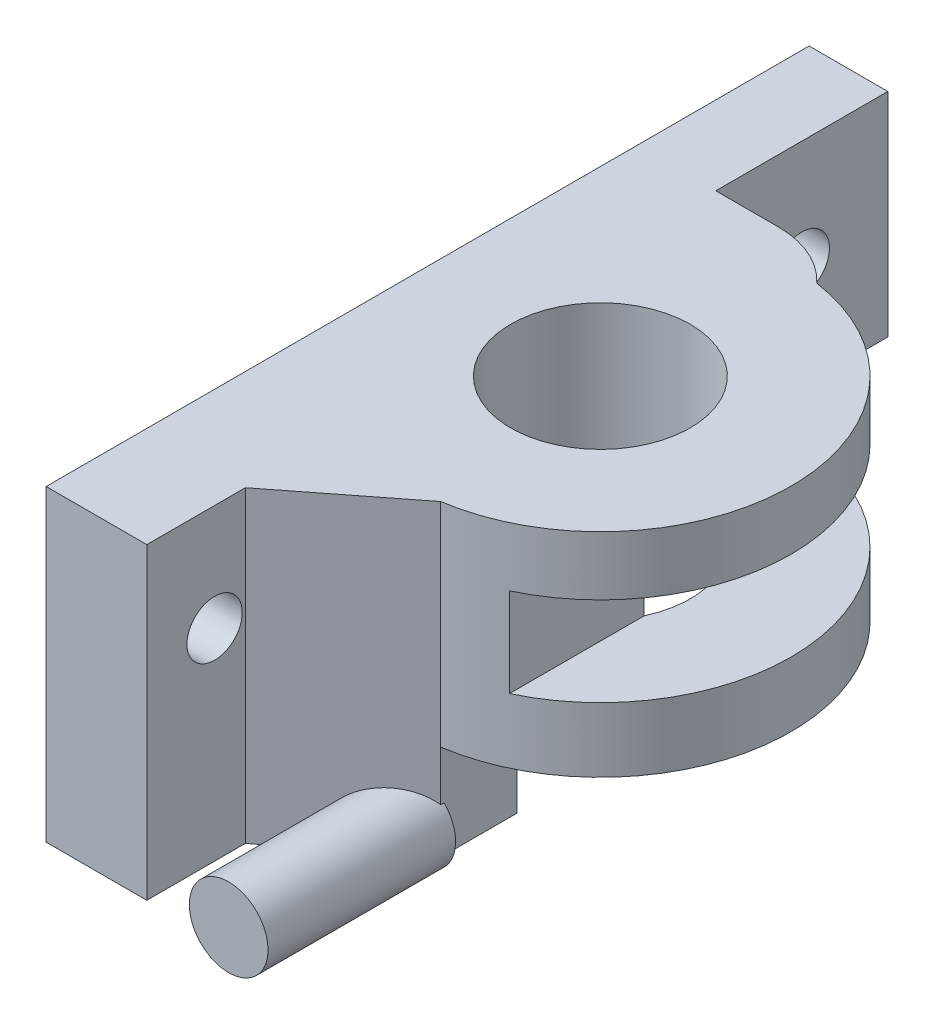
SolidWorks part; units mm, degrees
ref_plane "前基準面" through (0, 0, 0) normal (0, 0, 1) x (1, 0, 0)
ref_plane "上基準面" through (0, 0, 0) normal (0, 1, 0) x (1, 0, 0)
ref_plane "右基準面" through (0, 0, 0) normal (1, 0, 0) x (0, 0, -1)
sketch "草圖1" plane through (0, 0, 0) normal (0, 1, 0) x (1, 0, 0)
  circle A0 centre (0, 0) radius 9.68
  dimension "D1" = 19.36
extrude "伸長-薄件1" add sketch "草圖1" along normal blind 116.68 thin thin type one direction wall 11
ref_plane "平面1" through (-21, 0, 0) normal (1, 0, 0) x (0, 0, -1)
sketch "草圖11" plane through (0, 116.68, 0) normal (0, 1, 0) x (1, 0, 0)
  line L0 (-993.1634, -44.2358) -> (49006.8366, -44.2358) construction
  line L2 (35.2085, 30.7642) -> (8.2085, 30.7642)
  line L3 (35.2085, 30.7642) -> (35.2085, -119.2358)
  line L4 (35.2085, -119.2358) -> (8.2085, -119.2358)
  line L5 (8.2085, 30.7642) -> (8.2085, -119.2358)
  line L6 (35.2085, 30.7642) -> (8.2085, -119.2358) construction
  line L7 (35.2085, -119.2358) -> (8.2085, 30.7642) construction
  circle A0 centre (0, 0) radius 20.68 construction
  point P1 (21.7085, -44.2358)
  dimension "D1" = 150
  dimension "D2" = 27
  dimension "D3" = 30.7642
extrude "除料-伸長3" cut sketch "草圖11" against normal blind 40
ref_plane "平面2" through (0, 0, 21) normal (0, 0, 1) x (1, 0, 0)
sketch "草圖13" plane through (0, 0, 21) normal (0, 0, 1) x (1, 0, 0)
  line L0 (-21, -22.649) -> (-21, 22.649) construction
  line L1 (-21, 122.7847) -> (-11, 122.7847)
  line L2 (-21, 122.7847) -> (-21, -5.5603)
  line L3 (-21, -5.5603) -> (-11, -5.5603)
  line L4 (-11, 122.7847) -> (-11, -5.5603)
  dimension "D1" = 10
extrude "除料-伸長7" cut sketch "草圖13" against normal through all
sketch "草圖15" plane through (0, 0, 21) normal (0, 0, 1) x (1, 0, 0)
  line L0 (-1.3957, -883.32) -> (-1.3957, 49116.68) construction
  line L1 (8.2085, 116.68) -> (-11, 116.68) construction
  line L2 (-11, 0) -> (20.68, 0) construction
  line L3 (2.6043, 86.68) -> (-5.3957, 86.68)
  line L4 (2.6043, 86.68) -> (2.6043, 18)
  line L5 (2.6043, 18) -> (-5.3957, 18)
  line L6 (-5.3957, 86.68) -> (-5.3957, 18)
  line L7 (2.6043, 86.68) -> (-5.3957, 18) construction
  line L8 (2.6043, 18) -> (-5.3957, 86.68) construction
  point P1 (-1.3957, 52.34)
  point P5 (-1.3957, 116.68)
  dimension "D1" = 30
  dimension "D2" = 18
  dimension "D3" = 8
extrude "除料-伸長9" cut sketch "草圖15" against normal blind 48
sketch "草圖16" plane through (8.2085, 0, 0) normal (1, 0, 0) x (0, 0, -1)
  line L0 (20.68, 86.68) -> (20.68, 116.68) construction
  line L1 (5.1306, 116.68) -> (20.68, 116.68)
  line L2 (5.1306, 116.68) -> (5.1306, 96.68)
  line L3 (5.1306, 96.68) -> (20.68, 96.68)
  line L4 (20.68, 116.68) -> (20.68, 96.68)
  line L5 (-5.1306, 76.68) -> (-5.1306, 116.68) construction
  line L6 (-5.1306, 96.68) -> (-20.59, 96.68)
  line L7 (-5.1306, 96.68) -> (-5.1306, 116.68)
  line L8 (-5.1306, 116.68) -> (-20.59, 116.68)
  line L9 (-20.59, 96.68) -> (-20.59, 116.68)
  line L10 (-17.5118, 116.68) -> (-20.68, 116.68) construction
  dimension "D1" = 20
extrude "填料-伸長4" add sketch "草圖16" against normal blind 19.2
sketch "草圖17" plane through (0, 116.68, 0) normal (0, 1, 0) x (1, 0, 0)
  line L0 (-1009.59, 0) -> (48990.41, 0) construction
  line L1 (8.2085, 20.68) -> (8.2085, 5.1306) construction
  line L2 (8.2085, 6.97) -> (-11, 6.97)
  line L3 (8.2085, 6.97) -> (8.2085, -7.06)
  line L4 (8.2085, -7.06) -> (-11, -7.06)
  line L5 (-11, 6.97) -> (-11, -7.06)
  line L6 (-11, -17.5118) -> (-11, 17.5118) construction
  line L7 (-10.9915, -20.59) -> (-1.9273, -20.59) construction
  arc A0 (-8.2085, 5.1306) -> (-8.2085, -5.1306) centre (0, 0) ccw construction
  point P6 (-9.68, 0)
  dimension "D1" = 14.03
  dimension "D2" = 13.53
extrude "除料-伸長10" cut sketch "草圖17" against normal blind 20.2
sketch "草圖18" plane through (0, 0, 0) normal (0, -1, 0) x (1, 0, 0)
  circle A0 centre (0, 0) radius 9.59
extrude "除料-伸長11" cut sketch "草圖18" against normal through all
sketch "草圖21" plane through (0, 0, -20.68) normal (0, 0, -1) x (-1, 0, 0)
  line L0 (1.3915, 96.68) -> (1.3915, 105.73) construction
  line L1 (0, 96.68) -> (10.9915, 96.68) construction
  line L2 (1.3915, 105.73) -> (1.3915, 108.73) construction
  circle A0 centre (1.3915, 108.73) radius 2.985
  dimension "D3" = 5.97
  dimension "D1" = 9.05
  dimension "D2" = 3
extrude "除料-伸長12" cut sketch "草圖21" against normal blind 55.2
sketch "草圖23" plane through (0, 0, -20.68) normal (0, 0, -1) x (-1, 0, 0)
  line L0 (1.3915, 105.745) -> (1.3915, -11.785) construction
  circle A0 centre (1.3915, 108.73) radius 2.985 construction
  dimension "D1" = 117.53
sketch "草圖24" plane through (0, 0, 0) normal (0, -1, 0) x (1, 0, 0)
  circle A0 centre (0, 0) radius 9.59
extrude "伸長-薄件2" add sketch "草圖24" along normal blind 55.2 thin thin type one direction wall 11
sketch "草圖25" plane through (0, 0, 21) normal (0, 0, 1) x (1, 0, 0)
  line L0 (-1.3915, -11.785) -> (22.6124, -11.785)
  line L1 (22.6124, -11.785) -> (22.6124, -63.8733)
  line L2 (-22.7495, -63.8733) -> (22.6124, -63.8733)
  line L3 (-22.7495, -63.8733) -> (-22.7495, -11.785)
  line L4 (-22.7495, -11.785) -> (-1.3915, -11.785)
extrude "除料-伸長13" cut sketch "草圖25" against normal blind 55.2
sketch "草圖26" plane through (0, 0, 0) normal (0, 1, 0) x (1, 0, 0)
  line L0 (-21, -22.649) -> (-21, 22.649) construction
  line L1 (-10.9915, 20.68) -> (-21, 20.68)
  line L2 (-10.9915, 20.68) -> (-10.9915, -21)
  line L3 (-10.9915, -21) -> (-21, -21)
  line L4 (-21, 20.68) -> (-21, -21)
  line L5 (-17.6, -21) -> (17.6, -21) construction
extrude "除料-伸長15" cut sketch "草圖26" against normal blind 55.2
ref_plane "平面3" through (21, 0, 0) normal (1, 0, 0) x (0, 0, -1)
sketch "草圖27" plane through (21, 0, 0) normal (1, 0, 0) x (0, 0, -1)
  line L0 (0, -923.32) -> (0, 49076.68) construction
  line L1 (5.1306, 76.68) -> (-5.1306, 76.68) construction
  line L2 (18.9811, 76.68) -> (-18.9811, 76.68) construction
  line L3 (-5, 61.68) -> (5, 61.68)
  line L4 (-5, 61.68) -> (-5, 21.68)
  line L5 (-5, 21.68) -> (5, 21.68)
  line L6 (5, 61.68) -> (5, 21.68)
  line L7 (-5, 61.68) -> (5, 21.68) construction
  line L8 (-5, 21.68) -> (5, 61.68) construction
  point P1 (0, 41.68)
  point P5 (0, 76.68)
  dimension "D1" = 15
  dimension "D2" = 40
  dimension "D3" = 10
extrude "除料-伸長16" cut sketch "草圖27" against normal blind 55.2
sketch "草圖28" plane through (21, 0, 0) normal (1, 0, 0) x (0, 0, -1)
  line L1 (-22.4403, 4.804) -> (22.4403, 4.804)
  line L2 (-22.4403, 4.804) -> (-22.4403, -4.804)
  line L3 (-22.4403, -4.804) -> (22.4403, -4.804)
  line L4 (22.4403, 4.804) -> (22.4403, -4.804)
  line L5 (-22.4403, 4.804) -> (22.4403, -4.804) construction
  line L6 (-22.4403, -4.804) -> (22.4403, 4.804) construction
  point P0 (0, 0)
extrude "除料-伸長17" cut sketch "草圖28" against normal blind 12.2
sketch "草圖35" plane through (-10.9915, 0, 0) normal (-1, 0, 0) x (0, 0, 1)
  line L0 (20.59, 116.68) -> (20.59, 96.68)
  line L1 (20.59, 96.68) -> (7.06, 96.68)
  line L2 (7.06, 96.68) -> (7.06, 116.68)
  line L3 (7.06, 116.68) -> (20.59, 116.68)
extrude "填料-伸長10" add sketch "草圖35" along normal blind 15
sketch "草圖36" plane through (-10.9915, 0, 0) normal (-1, 0, 0) x (0, 0, 1)
  line L0 (-20.68, 116.68) -> (-6.97, 116.68)
  line L1 (-6.97, 116.68) -> (-6.97, 96.48)
  line L2 (-6.97, 96.48) -> (-20.68, 96.68)
  line L3 (-20.68, 96.68) -> (-20.68, 116.68)
extrude "填料-伸長11" add sketch "草圖36" along normal blind 15
sketch "草圖37" plane through (0, 0, 20.59) normal (0, 0, 1) x (1, 0, 0)
  line L0 (-25.9915, 96.68) -> (-1.9273, 96.68) construction
  line L1 (-25.9915, 116.68) -> (-16.9915, 116.68)
  line L2 (-25.9915, 116.68) -> (-25.9915, 96.68)
  line L3 (-25.9915, 96.68) -> (-16.9915, 96.68)
  line L4 (-16.9915, 116.68) -> (-16.9915, 96.68)
  dimension "D1" = 9
extrude "填料-伸長12" add sketch "草圖37" along normal blind 20
sketch "草圖38" plane through (0, 0, -20.68) normal (0, 0, -1) x (-1, 0, 0)
  line L0 (25.9915, 116.68) -> (-8.2085, 116.68) construction
  line L1 (25.9915, 96.68) -> (16.9915, 96.68)
  line L2 (25.9915, 96.68) -> (25.9915, 116.68)
  line L3 (25.9915, 116.68) -> (16.9915, 116.68)
  line L4 (16.9915, 96.68) -> (16.9915, 116.68)
  dimension "D1" = 9
extrude "填料-伸長13" add sketch "草圖38" along normal blind 20
sketch "草圖42" plane through (-16.9915, 0, 0) normal (1, 0, 0) x (0, 0, -1)
  line L0 (30.68, -903.32) -> (30.68, 49096.68) construction
  line L1 (40.68, 96.68) -> (20.68, 96.68) construction
  line L2 (-959.32, 106.68) -> (49040.68, 106.68) construction
  line L3 (40.68, 116.68) -> (40.68, 96.68) construction
  line L4 (-30.59, -903.32) -> (-30.59, 49096.68) construction
  line L5 (-40.59, 96.68) -> (-20.59, 96.68) construction
  circle A0 centre (30.68, 106.5544) radius 2.985
  circle A1 centre (-30.3956, 106.68) radius 2.985
  point P5 (30.68, 96.68)
  point P10 (40.68, 106.68)
  point P15 (-30.59, 96.68)
  dimension "D1" = 5.97
  dimension "D2" = 5.97
extrude "除料-伸長21" cut sketch "草圖42" against normal blind 20
sketch "草圖43" plane through (0, 116.68, 0) normal (0, 1, 0) x (1, 0, 0)
  line L0 (-11, 6.97) -> (-10.9915, 20.68)
  line L1 (-10.9915, 20.68) -> (-10.9915, 48.0968)
  line L2 (-10.9915, 48.0968) -> (-28.2748, 48.0968)
  line L3 (-28.2748, 48.0968) -> (-28.2748, -43.2705)
  line L4 (-28.2748, -43.2705) -> (-11, -43.2705)
  line L5 (-11, -43.2705) -> (-11, 6.97)
extrude "除料-伸長23" cut sketch "草圖43" against normal through all
sketch "草圖45" plane through (0, 0, 20.59) normal (0, 0, 1) x (1, 0, 0)
  line L0 (-11, 96.68) -> (-1.9273, 96.68) construction
  line L1 (-11, 116.68) -> (-8, 116.68)
  line L2 (-11, 116.68) -> (-11, 96.68)
  line L3 (-11, 96.68) -> (-8, 96.68)
  line L4 (-8, 116.68) -> (-8, 96.68)
  dimension "D1" = 3
extrude "填料-伸長14" add sketch "草圖45" along normal blind 30
sketch "草圖46" plane through (0, 0, -20.68) normal (0, 0, -1) x (-1, 0, 0)
  line L0 (0, 96.68) -> (10.9915, 96.68) construction
  line L1 (10.9915, 116.68) -> (7.9915, 116.68)
  line L2 (10.9915, 116.68) -> (10.9915, 96.68)
  line L3 (10.9915, 96.68) -> (7.9915, 96.68)
  line L4 (7.9915, 116.68) -> (7.9915, 96.68)
  dimension "D1" = 3
extrude "填料-伸長15" add sketch "草圖46" along normal blind 30
sketch "草圖47" plane through (-11, 0, 0) normal (-1, 0, 0) x (0, 0, 1)
  line L0 (50.59, 116.68) -> (7.06, 116.68) construction
  line L1 (50.59, 96.68) -> (17.5118, 96.68)
  line L2 (50.59, 96.68) -> (50.59, 116.68)
  line L3 (50.59, 116.68) -> (17.5118, 116.68)
  line L4 (17.5118, 96.68) -> (17.5118, 116.68)
extrude "填料-伸長16" add sketch "草圖47" along normal blind 50
sketch "草圖48" plane through (-10.9915, 0, 0) normal (-1, 0, 0) x (0, 0, 1)
  line L1 (-50.68, 116.68) -> (-20.68, 116.68)
  line L2 (-50.68, 116.68) -> (-50.68, 96.68)
  line L3 (-50.68, 96.68) -> (-20.68, 96.68)
  line L4 (-20.68, 116.68) -> (-20.68, 96.68)
extrude "填料-伸長17" add sketch "草圖48" along normal blind 50
sketch "草圖50" plane through (0, 0, 17.5118) normal (0, 0, -1) x (-1, 0, 0)
  line L0 (11, 96.68) -> (11, 116.68)
  line L1 (11, 116.68) -> (61, 116.68)
  line L2 (61, 116.68) -> (61, 96.68)
  line L3 (61, 96.68) -> (11, 96.68)
extrude "填料-伸長18" add sketch "草圖50" along normal blind 1
sketch "草圖51" plane through (0, 0, -20.68) normal (0, 0, 1) x (1, 0, 0)
  line L0 (-10.9915, 116.68) -> (-10.9915, 96.68)
  line L1 (-10.9915, 96.68) -> (-60.9915, 96.68)
  line L2 (-60.9915, 96.68) -> (-60.9915, 116.68)
  line L3 (-60.9915, 116.68) -> (-10.9915, 116.68)
extrude "填料-伸長19" add sketch "草圖51" along normal blind 1
sketch "草圖52" plane through (0, 116.68, 0) normal (0, 1, 0) x (1, 0, 0)
  line L0 (-34.4915, -949.32) -> (-34.4915, 49050.68) construction
  line L1 (-60.9915, 50.68) -> (-7.9915, 50.68) construction
  line L2 (-1007.9915, 35.68) -> (48992.0085, 35.68) construction
  line L3 (-7.9915, 50.68) -> (-7.9915, 20.68) construction
  line L4 (-60.9915, 19.68) -> (-60.9915, 50.68) construction
  line L5 (-7.9915, 50.68) -> (-60.9915, 50.68)
  line L6 (-7.9915, 50.68) -> (-7.9915, 36.68)
  line L7 (-7.9915, 36.68) -> (-60.9915, 36.68)
  line L8 (-60.9915, 50.68) -> (-60.9915, 36.68)
  point P5 (-34.4915, 50.68)
  point P10 (-7.9915, 35.68)
  dimension "D1" = 14
extrude "除料-伸長24" cut sketch "草圖52" against normal through all
sketch "草圖53" plane through (0, 116.68, 0) normal (0, 1, 0) x (1, 0, 0)
  line L0 (-61, -50.59) -> (-61, -16.5118) construction
  line L1 (-8, -50.59) -> (-61, -50.59)
  line L2 (-8, -50.59) -> (-8, -36.59)
  line L3 (-8, -36.59) -> (-61, -36.59)
  line L4 (-61, -50.59) -> (-61, -36.59)
  dimension "D1" = 14
extrude "除料-伸長25" cut sketch "草圖53" against normal through all
sketch "草圖54" plane through (0, 116.68, 0) normal (0, 1, 0) x (1, 0, 0)
  line L0 (-60.9915, 36.68) -> (-7.9915, 36.68) construction
  line L1 (-61, -36.59) -> (-21, -36.59)
  line L2 (-61, -36.59) -> (-61, 36.68)
  line L3 (-61, 36.68) -> (-21, 36.68)
  line L4 (-21, -36.59) -> (-21, 36.68)
  dimension "D1" = 40
extrude "除料-伸長26" cut sketch "草圖54" against normal through all
sketch "草圖55" plane through (0, 116.68, 0) normal (0, 1, 0) x (1, 0, 0)
  line L0 (-15.0276, -36.59) -> (-15.0276, -16.5118) construction
  line L1 (-8, -36.59) -> (-21, -36.59) construction
  line L2 (-21, -16.5118) -> (-11, -16.5118) construction
  line L3 (-13.4574, 19.68) -> (-13.4574, 39.76) construction
  line L4 (-10.9921, 19.68) -> (-21, 19.68) construction
  dimension "D1" = 20.08
sketch "草圖56" plane through (0, 0, -36.68) normal (0, 0, -1) x (-1, 0, 0)
  line L1 (7.9915, 96.68) -> (21, 96.68)
  line L2 (7.9915, 96.68) -> (7.9915, 116.68)
  line L3 (7.9915, 116.68) -> (21, 116.68)
  line L4 (21, 96.68) -> (21, 116.68)
extrude "填料-伸長21" add sketch "草圖56" along normal blind 3.08
ref_plane "平面4" through (0, 0, 50) normal (0, 0, 1) x (1, 0, 0)
sketch "草圖60" plane through (0, 116.68, 0) normal (0, 1, 0) x (1, 0, 0)
  line L0 (-21, 39.76) -> (-7.9915, 39.76) construction
  line L1 (-21, -36.59) -> (-14.4957, -36.59)
  line L2 (-21, -36.59) -> (-21, 39.76)
  line L3 (-21, 39.76) -> (-14.4957, 39.76)
  line L4 (-14.4957, -36.59) -> (-14.4957, 39.76)
extrude "除料-伸長30" cut sketch "草圖60" against normal through all
sketch "草圖61" plane through (0, 116.68, 0) normal (0, 1, 0) x (1, 0, 0)
  line L0 (1.9273, -20.59) -> (1.9273, -22.3991)
  line L1 (1.9273, -22.3991) -> (-2.1742, -21.4215)
  line L2 (-2.1742, -21.4215) -> (-2.1742, -20.59)
  line L3 (-8, -20.59) -> (-1.9273, -20.59) construction
  line L4 (-2.1742, -20.59) -> (1.9273, -20.59)
extrude "除料-伸長32" cut sketch "草圖61" against normal blind 20
sketch "草圖64" plane through (0, 116.68, 0) normal (0, 1, 0) x (1, 0, 0)
  line L1 (-8, -20.59) -> (8.2085, -20.59)
  line L2 (-8, -20.59) -> (-8, -20.68)
  line L3 (-8, -20.68) -> (8.2085, -20.68)
  line L4 (8.2085, -20.59) -> (8.2085, -20.68)
  dimension "D1" = 0.09
extrude "填料-伸長22" add sketch "草圖64" against normal blind 20
sketch "草圖65" plane through (0, 116.68, 0) normal (0, 1, 0) x (1, 0, 0)
  line L0 (-11, 6.97) -> (-10.9921, 19.68) construction
  line L1 (-11, -7.06) -> (-11, -16.5118) construction
  line L2 (-14.4957, -36.59) -> (-14.4957, -16.5118) construction
  line L3 (-11, -16.5118) -> (-14.4957, -16.5118)
  line L4 (-11, -16.5118) -> (-11, -19.7718)
  line L5 (-11, -19.7718) -> (-14.4957, -19.7718)
  line L6 (-14.4957, -16.5118) -> (-14.4957, -19.7718)
  dimension "D1" = 12.71
  dimension "D2" = 9.4518
  dimension "D3" = 3.26
extrude "除料-伸長33" cut sketch "草圖65" against normal through all
sketch "草圖66" plane through (0, 96.48, 0) normal (0, 1, 0) x (1, 0, 0)
  line L0 (-1011, -0.045) -> (48989, -0.045) construction
  line L1 (-11, 6.97) -> (-11, -7.06) construction
  line L2 (-12.9194, -0.045) -> (-12.9194, 17.905) construction
  line L3 (-12.9194, -0.045) -> (-12.9194, -17.995) construction
  line L4 (-11, -19.7718) -> (-11, -7.06) construction
  line L5 (-14.4957, -19.7718) -> (-11, -19.7718)
  line L6 (-14.4957, -19.7718) -> (-14.4957, -17.995)
  line L7 (-14.4957, -17.995) -> (-11, -17.995)
  line L8 (-11, -19.7718) -> (-11, -17.995)
  line L10 (-10.9921, 19.68) -> (-14.4957, 19.68)
  line L11 (-10.9921, 19.68) -> (-10.9921, 17.905)
  line L12 (-10.9921, 17.905) -> (-14.4957, 17.905)
  line L13 (-14.4957, 19.68) -> (-14.4957, 17.905)
  point P5 (-11, -0.045)
  dimension "D1" = 17.95
  dimension "D2" = 17.95
extrude "填料-伸長23" add sketch "草圖66" along normal blind 20.2
sketch "草圖68" plane through (0, 116.68, 0) normal (0, 1, 0) x (1, 0, 0)
  line L0 (-10.9932, 17.905) -> (-10.9932, 39.76) construction
  line L1 (-14.4957, 39.76) -> (-7.9915, 39.76) construction
  line L2 (-14.4957, 17.905) -> (-14.4957, 39.76) construction
  line L3 (-7.9915, 39.76) -> (-14.4957, 39.76)
  line L4 (-7.9915, 39.76) -> (-7.9915, 36.1)
  line L5 (-7.9915, 36.1) -> (-14.4957, 36.1)
  line L6 (-14.4957, 39.76) -> (-14.4957, 36.1)
  dimension "D1" = 3.66
extrude "除料-伸長34" cut sketch "草圖68" against normal blind 20
sketch "草圖69" plane through (-7.9915, 0, 0) normal (1, 0, 0) x (0, 0, -1)
  line L0 (28.39, -903.32) -> (28.39, 49096.68) construction
  line L1 (36.1, 96.68) -> (20.68, 96.68) construction
  line L2 (-28.635, -903.32) -> (-28.635, 49096.68) construction
  line L3 (-36.59, 96.68) -> (-20.68, 96.68) construction
  line L4 (-963.9, 106.68) -> (49036.1, 106.68) construction
  line L5 (36.1, 96.68) -> (36.1, 116.68) construction
  circle A0 centre (28.39, 106.68) radius 2.985
  circle A1 centre (-28.635, 106.68) radius 2.985
  point P5 (28.39, 96.68)
  point P10 (-28.635, 96.68)
  point P15 (36.1, 106.68)
  dimension "D1" = 5.97
  dimension "D2" = 5.97
extrude "除料-伸長35" cut sketch "草圖69" against normal through all
sketch "草圖70" plane through (0, 0, 20.59) normal (0, 0, -1) x (-1, 0, 0)
  circle A0 centre (1.3915, 108.73) radius 2.985
  dimension "D1" = 5.97
extrude "除料-伸長36" cut sketch "草圖70" against normal through all
sketch "草圖71" plane through (0, 0, 50) normal (0, 0, 1) x (1, 0, 0)
  line L1 (-16.2413, 123.1465) -> (21.764, 123.1465)
  line L2 (-16.2413, 123.1465) -> (-16.2413, 11.1806)
  line L3 (-16.2413, 11.1806) -> (21.764, 11.1806)
  line L4 (21.764, 123.1465) -> (21.764, 11.1806)
extrude "除料-伸長37" cut sketch "草圖71" against normal through all
sketch "草圖72" plane through (0, -11.785, 0) normal (0, -1, 0) x (1, 0, 0)
  circle A0 centre (0, 0) radius 9.7
  dimension "D1" = 19.4
extrude "除料-伸長38" cut sketch "草圖72" against normal through all
sketch "草圖77" plane through (0, 11.1806, 0) normal (0, 1, 0) x (1, 0, 0)
  circle A0 centre (0, 0) radius 20.59
  dimension "D1" = 41.18
extrude "除料-伸長-薄件2" cut sketch "草圖77" against normal blind 22 thin thin type one direction wall 10
sketch "草圖78" plane through (-11, 0, 0) normal (-1, 0, 0) x (0, 0, 1)
  line L1 (17.4054, 11.1806) -> (-17.4108, 11.1806)
  line L2 (17.4054, 11.1806) -> (17.4054, -11.785)
  line L3 (17.4054, -11.785) -> (-17.4108, -11.785)
  line L4 (-17.4108, 11.1806) -> (-17.4108, -11.785)
extrude "填料-伸長26" add sketch "草圖78" along normal blind 0.1
sketch "草圖80" plane through (0, -11.785, 0) normal (0, -1, 0) x (1, 0, 0)
  line L1 (-11.1, -17.4108) -> (-14, -17.4108)
  line L2 (-11.1, -17.4108) -> (-11.1, -23.5595)
  line L3 (-11.1, -23.5595) -> (-14, -23.5595)
  line L4 (-14, -17.4108) -> (-14, -23.5595)
extrude "填料-伸長28" add sketch "草圖80" against normal blind 23.1 separate body
sketch "草圖81" plane through (-11.1, 0, 0) normal (1, 0, 0) x (0, 0, -1)
  line L0 (17.4108, -11.785) -> (23.5595, -11.785)
  line L1 (23.5595, -11.785) -> (23.5595, 11.315)
  line L2 (23.5595, 11.315) -> (17.4108, 11.315)
  line L3 (17.4108, 11.315) -> (17.4108, -11.785)
extrude "填料-伸長29" add sketch "草圖81" along normal blind 14.1
sketch "草圖82" plane through (3, 0, 0) normal (1, 0, 0) x (0, 0, -1)
  line L0 (17.4108, 11.1806) -> (17.4108, 11.315)
  line L1 (17.4108, 11.315) -> (23.5595, 11.315)
  line L2 (23.5595, 11.315) -> (23.5595, 11.1806)
  line L3 (23.5595, -11.785) -> (23.5595, 11.315) construction
  line L4 (23.5595, 11.1806) -> (17.4108, 11.1806)
extrude "除料-伸長39" cut sketch "草圖82" against normal blind 19.1
sketch "草圖83" plane through (0, 0, -17.4108) normal (0, 0, 1) x (1, 0, 0)
  line L1 (-11.1, 11.1806) -> (-14, 11.1806)
  line L2 (-11.1, 11.1806) -> (-11.1, -11.785)
  line L3 (-11.1, -11.785) -> (-14, -11.785)
  line L4 (-14, 11.1806) -> (-14, -11.785)
extrude "填料-伸長30" add sketch "草圖83" against normal blind 19.1
fillet "圓角1" radius 10 1 edges at (3, -0.3022, -23.5595)
sketch "草圖84" plane through (0, -11.785, 0) normal (0, -1, 0) x (-1, 0, 0)
  line L1 (11.1, 17.4108) -> (14.6, 17.4108)
  line L2 (11.1, 17.4108) -> (11.1, 36.5108)
  line L3 (11.1, 36.5108) -> (14.6, 36.5108)
  line L4 (14.6, 17.4108) -> (14.6, 36.5108)
  dimension "D1" = 3.5
extrude "填料-伸長31" add sketch "草圖84" against normal blind 23.1
sketch "草圖85" plane through (0, -11.785, 0) normal (0, -1, 0) x (1, 0, 0)
  line L0 (-11.1, -17.4108) -> (-11.1, -35.9908) construction
  line L1 (-11.1, -36.5108) -> (-11.1, -23.5595) construction
  line L3 (-11.1, -35.9908) -> (-14.6, -35.9908)
  line L4 (-11.1, -35.9908) -> (-11.1, -36.5108)
  line L5 (-11.1, -36.5108) -> (-14.6, -36.5108)
  line L6 (-14.6, -35.9908) -> (-14.6, -36.5108)
  dimension "D1" = 18.58
extrude "除料-伸長40" cut sketch "草圖85" against normal through all
sketch "草圖86" plane through (0, 0, -17.4108) normal (0, 0, 1) x (1, 0, 0)
  line L1 (-11.1, 11.1806) -> (-14.6, 11.1806)
  line L2 (-11.1, 11.1806) -> (-11.1, -11.785)
  line L3 (-11.1, -11.785) -> (-14.6, -11.785)
  line L4 (-14.6, 11.1806) -> (-14.6, -11.785)
extrude "填料-伸長32" add sketch "草圖86" along normal blind 62.1
sketch "草圖87" plane through (0, -11.785, 0) normal (0, -1, 0) x (1, 0, 0)
  line L0 (-14.6, 44.6892) -> (-14.6, -35.9908) construction
  line L1 (-10.9915, -17.4108) -> (-14.6, -17.4108)
  line L2 (-10.9915, -17.4108) -> (-10.9915, 17.4054)
  line L3 (-10.9915, 17.4054) -> (-14.6, 17.4054)
  line L4 (-14.6, -17.4108) -> (-14.6, 17.4054)
extrude "除料-伸長41" cut sketch "草圖87" against normal blind 62.1
sketch "草圖89" plane through (0, -11.785, 0) normal (0, -1, 0) x (1, 0, 0)
  line L0 (-10.9915, 17.4108) -> (-10.9915, 23.5608) construction
  line L1 (-11.1, 44.6892) -> (-11.1, 17.4054) construction
  line L2 (-11.1, 23.5608) -> (-10.9915, 23.5608)
  line L3 (-11.1, 23.5608) -> (-11.1, 17.4108)
  line L4 (-11.1, 17.4108) -> (-10.9915, 17.4108)
  line L5 (-10.9915, 23.5608) -> (-10.9915, 17.4108)
  dimension "D1" = 6.15
extrude "填料-伸長33" add sketch "草圖89" against normal blind 23.1
sketch "草圖90" plane through (0, 0, 23.5608) normal (0, 0, 1) x (1, 0, 0)
  line L0 (-11, 11.1806) -> (-11.1, 11.1806)
  line L1 (-11.1, 11.1806) -> (-11.1, -11.785)
  line L2 (-11.1, -11.785) -> (-10.9915, -11.785)
  line L3 (-10.9915, -11.785) -> (-10.9915, 11.1806)
  line L4 (-10.9915, 11.1806) -> (-11, 11.1806)
extrude "填料-伸長34" add sketch "草圖90" along normal blind 22.1
sketch "草圖91" plane through (-11.1, 0, 0) normal (-1, 0, 0) x (0, 0, 1)
  line L1 (45.6608, -11.785) -> (44.6892, -11.785)
  line L2 (45.6608, -11.785) -> (45.6608, 11.1806)
  line L3 (45.6608, 11.1806) -> (44.6892, 11.1806)
  line L4 (44.6892, -11.785) -> (44.6892, 11.1806)
extrude "除料-伸長42" cut sketch "草圖91" against normal blind 22.1
sketch "草圖93" plane through (0, -11.785, 0) normal (0, -1, 0) x (1, 0, 0)
  line L0 (-10.9915, 17.4108) -> (-10.9915, 23.5608) construction
  line L1 (-10.9915, 17.4108) -> (-10.9915, 44.6892) construction
  dimension "D1" = 6.15
sketch "草圖94" plane through (-10.9915, 0, 0) normal (1, 0, 0) x (0, 0, -1)
  line L0 (-23.5608, -11.785) -> (-23.5608, 11.1806) construction
  line L1 (-17.4108, -11.785) -> (-23.5608, -11.785) construction
sketch "草圖95" plane through (-10.9915, 0, 0) normal (1, 0, 0) x (0, 0, -1)
  line L1 (-23.5608, 11.1806) -> (-17.4108, 11.1806)
  line L2 (-17.4108, 11.315) -> (-17.4108, -11.785) construction
  line L3 (-17.4108, 11.1806) -> (-17.4108, -11.785)
  line L4 (-17.4108, -11.785) -> (-23.5608, -11.785)
  line L5 (-23.5608, -11.785) -> (-23.5608, 11.1806)
extrude "填料-伸長35" add sketch "草圖95" along normal blind 14.1
fillet "圓角2" radius 10 1 edges at (3.1085, -0.3022, 23.5608)
sketch "草圖96" plane through (0, -11.785, 0) normal (0, -1, 0) x (1, 0, 0)
  line L0 (-10.9915, 23.5608) -> (-10.9915, 42.1408) construction
  line L1 (-10.9915, 23.5608) -> (-10.9915, 44.6892) construction
  line L3 (-10.9915, 42.1408) -> (-14.6, 42.1408)
  line L4 (-10.9915, 42.1408) -> (-10.9915, 44.6892)
  line L5 (-10.9915, 44.6892) -> (-14.6, 44.6892)
  line L6 (-14.6, 42.1408) -> (-14.6, 44.6892)
  dimension "D1" = 18.58
extrude "除料-伸長43" cut sketch "草圖96" against normal through all
sketch "草圖97" plane through (0, -11.785, 0) normal (0, -1, 0) x (1, 0, 0)
  line L0 (-11.1, -23.5595) -> (-11.1, -42.1395) construction
  line L2 (-14.6, -35.9908) -> (-11.1, -35.9908)
  line L3 (-14.6, -35.9908) -> (-14.6, -42.1395)
  line L4 (-14.6, -42.1395) -> (-11.1, -42.1395)
  line L5 (-11.1, -35.9908) -> (-11.1, -42.1395)
  dimension "D1" = 18.58
extrude "填料-伸長36" add sketch "草圖97" against normal blind 23.1
sketch "草圖98" plane through (-11.1, 0, 0) normal (1, 0, 0) x (0, 0, -1)
  line L0 (17.4108, 11.1806) -> (17.4108, 11.315)
  line L1 (17.4108, 11.315) -> (22.1983, 11.315)
  line L2 (42.1395, 11.315) -> (17.4108, 11.315) construction
  line L3 (22.1983, 11.315) -> (38.4617, 11.315)
  line L4 (38.4617, 11.315) -> (42.1395, 11.315)
  line L5 (42.1395, 11.315) -> (42.1395, 11.1806)
  line L6 (42.1395, 11.315) -> (42.1395, -11.785) construction
  line L7 (42.1395, 11.1806) -> (17.4108, 11.1806)
extrude "除料-伸長44" cut sketch "草圖98" against normal blind 23.1
sketch "草圖99" plane through (-10.9915, 0, 0) normal (1, 0, 0) x (0, 0, -1)
  line L1 (-23.5608, 11.1806) -> (-17.4108, 11.1806)
  line L2 (-23.5608, 11.1806) -> (-23.5608, 11.315)
  line L3 (-23.5608, 11.315) -> (-17.4108, 11.315)
  line L4 (-17.4108, 11.1806) -> (-17.4108, 11.315)
extrude "除料-伸長45" cut sketch "草圖99" against normal blind 23.1
sketch "草圖100" plane through (-10.9915, 0, 0) normal (1, 0, 0) x (0, 0, -1)
  line L0 (-1042.1408, -0.3022) -> (48957.8592, -0.3022) construction
  line L1 (-42.1408, 11.1806) -> (-42.1408, -11.785) construction
  line L2 (-32.8508, -988.8194) -> (-32.8508, 49011.1806) construction
  line L3 (-42.1408, 11.1806) -> (-23.5608, 11.1806) construction
  line L4 (32.8495, -988.8194) -> (32.8495, 49011.1806) construction
  line L5 (23.5595, 11.1806) -> (42.1395, 11.1806) construction
  point P5 (-42.1408, -0.3022)
  point P10 (-32.8508, 11.1806)
  point P15 (32.8495, 11.1806)
sketch "草圖101" plane through (-10.9915, 0, 0) normal (1, 0, 0) x (0, 0, -1)
  line L0 (-201042.1408, -0.3022) -> (248957.8592, -0.3022) construction
  line L1 (32.8495, -200988.8194) -> (32.8495, 249011.1806) construction
  circle A0 centre (-32.9287, -0.3022) radius 2.985
  circle A1 centre (32.8495, -0.3022) radius 2.985
  dimension "D1" = 5.97
  dimension "D2" = 5.97
extrude "除料-伸長46" cut sketch "草圖101" against normal blind 23.1
sketch "草圖102" plane through (0, 11.1806, 0) normal (0, 1, 0) x (1, 0, 0)
  line L0 (-14.6, 42.1395) -> (-14.6, 17.4108) construction
  line L1 (-10.9915, 17.4108) -> (-14.6, 17.4108)
  line L2 (-10.9915, 17.4108) -> (-10.9915, 17.9508)
  line L3 (-10.9915, 17.9508) -> (-14.6, 17.9508)
  line L4 (-14.6, 17.4108) -> (-14.6, 17.9508)
  line L5 (-14.6, -42.1408) -> (-14.6, -17.4054) construction
  line L6 (-10.9915, -17.4108) -> (-14.6, -17.4108)
  line L7 (-10.9915, -17.4108) -> (-10.9915, -17.9508)
  line L8 (-10.9915, -17.9508) -> (-14.6, -17.9508)
  line L9 (-14.6, -17.4108) -> (-14.6, -17.9508)
  dimension "D1" = 0.54
  dimension "D2" = 0.54
sketch "草圖103" plane through (0, 11.1806, 0) normal (0, 1, 0) x (1, 0, 0)
  line L0 (-14.6, -17.4108) -> (-14.6, -17.9508) construction
  line L1 (-10.9915, -17.4054) -> (-14.6, -17.4054)
  line L2 (-10.9915, -17.4054) -> (-10.9915, -17.9454)
  line L3 (-10.9915, -17.9454) -> (-14.6, -17.9454)
  line L4 (-14.6, -17.4054) -> (-14.6, -17.9454)
  dimension "D1" = 0.54
extrude "除料-伸長49" cut sketch "草圖103" against normal through all
sketch "草圖104" plane through (0, 11.1806, 0) normal (0, 1, 0) x (1, 0, 0)
  line L0 (-14.6, 42.1395) -> (-14.6, 17.4108) construction
  line L1 (-10.9915, 17.4108) -> (-14.6, 17.4108)
  line L2 (-10.9915, 17.4108) -> (-10.9915, 17.9508)
  line L3 (-10.9915, 17.9508) -> (-14.6, 17.9508)
  line L4 (-14.6, 17.4108) -> (-14.6, 17.9508)
  dimension "D1" = 0.54
extrude "除料-伸長50" cut sketch "草圖104" against normal through all
sketch "草圖105" plane through (0, 0, 50) normal (0, 0, 1) x (1, 0, 0)
  line L1 (-10.9915, 11.1806) -> (3.1085, 11.1806)
  line L2 (-10.9915, 11.1806) -> (-10.9915, -11.785)
  line L3 (-10.9915, -11.785) -> (3.1085, -11.785)
  line L4 (3.1085, 11.1806) -> (3.1085, -11.785)
extrude "填料-伸長37" add sketch "草圖105" against normal blind 30
sketch "草圖106" plane through (-10.9915, 0, 0) normal (-1, 0, 0) x (0, 0, 1)
  line L0 (42.1408, -11.785) -> (50, -11.785) construction
  line L1 (42.1408, 11.1806) -> (50.4014, 11.1806)
  line L2 (42.1408, 11.1806) -> (42.1408, -11.785)
  line L3 (42.1408, -11.785) -> (50.4014, -11.785)
  line L4 (50.4014, 11.1806) -> (50.4014, -11.785)
  dimension "D1" = 0
extrude "除料-伸長52" cut sketch "草圖106" against normal through all
sketch "草圖107" plane through (-10.9915, 0, 0) normal (-1, 0, 0) x (0, 0, 1)
  line L0 (32.9287, -997.3172) -> (32.9287, 49002.6828) construction
  line L1 (-964.0863, -0.3022) -> (49035.9137, -0.3022) construction
  circle A4 centre (32.9287, -0.3022) radius 2.985
extrude "除料-伸長53" cut sketch "草圖107" against normal through all
sketch "草圖108" plane through (0, 0, 17.9454) normal (0, 0, -1) x (-1, 0, 0)
  line L0 (10.9915, -11.785) -> (14.6, -11.785)
  line L1 (14.6, -11.785) -> (14.6, 11.1806)
  line L2 (14.6, 11.1806) -> (10.9915, 11.1806)
  line L3 (10.9915, 11.1806) -> (10.9915, -11.785)
extrude "填料-伸長38" add sketch "草圖108" along normal blind 40
sketch "草圖109" plane through (-14.6, 0, 0) normal (-1, 0, 0) x (0, 0, 1)
  line L1 (-42.1395, -11.785) -> (42.1408, -11.785)
  line L2 (-42.1395, -11.785) -> (-42.1395, 11.1806)
  line L3 (-42.1395, 11.1806) -> (42.1408, 11.1806)
  line L4 (42.1408, -11.785) -> (42.1408, 11.1806)
extrude "填料-伸長39" add sketch "草圖109" along normal blind 5
sketch "草圖110" plane through (-14.6, 0, 0) normal (1, 0, 0) x (0, 0, -1)
  circle A0 centre (32.8495, -0.3022) radius 2.985
extrude "除料-伸長54" cut sketch "草圖110" against normal through all
sketch "草圖111" plane through (3.1085, 0, 0) normal (1, 0, 0) x (0, 0, -1)
  circle A0 centre (-32.9287, -0.3022) radius 2.985
extrude "除料-伸長55" cut sketch "草圖111" against normal through all
sketch "草圖112" plane through (0, 11.1806, 0) normal (0, 1, 0) x (1, 0, 0)
  line L0 (3.1085, -20.354) -> (-8.7306, -29.6073)
  line L1 (-8.7306, -29.6073) -> (-8.7306, -42.1408)
  line L2 (-19.6, -42.1408) -> (3.1085, -42.1408) construction
  line L3 (-8.7306, -42.1408) -> (3.1085, -42.1408)
  line L4 (3.1085, -42.1408) -> (3.1085, -20.354)
extrude "除料-伸長56" cut sketch "草圖112" against normal through all
sketch "草圖113" plane through (0, -11.785, 0) normal (0, -1, 0) x (1, 0, 0)
  line L0 (3.1085, 20.354) -> (-8.7306, 29.6073)
  line L1 (-8.7306, 29.6073) -> (-8.7306, 42.1408)
  line L2 (-8.7306, 42.1408) -> (-19.6, 42.1408)
  line L3 (-19.6, 42.1408) -> (-19.6, 12.0896)
  line L4 (-19.6, -42.1395) -> (-19.6, 42.1408) construction
  line L5 (-19.6, 12.0896) -> (3.1085, 12.0896)
  line L6 (3.1085, 12.0896) -> (3.1085, 20.354)
extrude "填料-伸長40" add sketch "草圖113" along normal blind 10.3
sketch "草圖120" plane through (0, 0, 50) normal (0, 0, 1) x (1, 0, 0)
  line L0 (3.1085, -22.085) -> (3.1085, -11.785) construction
  line L1 (3.1085, -22.085) -> (-8.7306, -22.085) construction
  circle A0 centre (0.1085, -20.185) radius 4.25
  dimension "D1" = 8.5
  dimension "D2" = 3
  dimension "D3" = 1.9
extrude "填料-伸長44" add sketch "草圖120" along normal blind 0.01 and the other way blind 30.01
sketch "草圖121" plane through (0, 0, 0) normal (0, 1, 0) x (1, 0, 0)
  line L1 (-21.4609, -54.9572) -> (27.7415, -54.9572)
  line L2 (-21.4609, -54.9572) -> (-21.4609, -40.2494)
  line L3 (-21.4609, -40.2494) -> (27.7415, -40.2494)
  line L4 (27.7415, -54.9572) -> (27.7415, -40.2494)
extrude "除料-伸長58" cut sketch "草圖121" against normal through all and the other way through all
